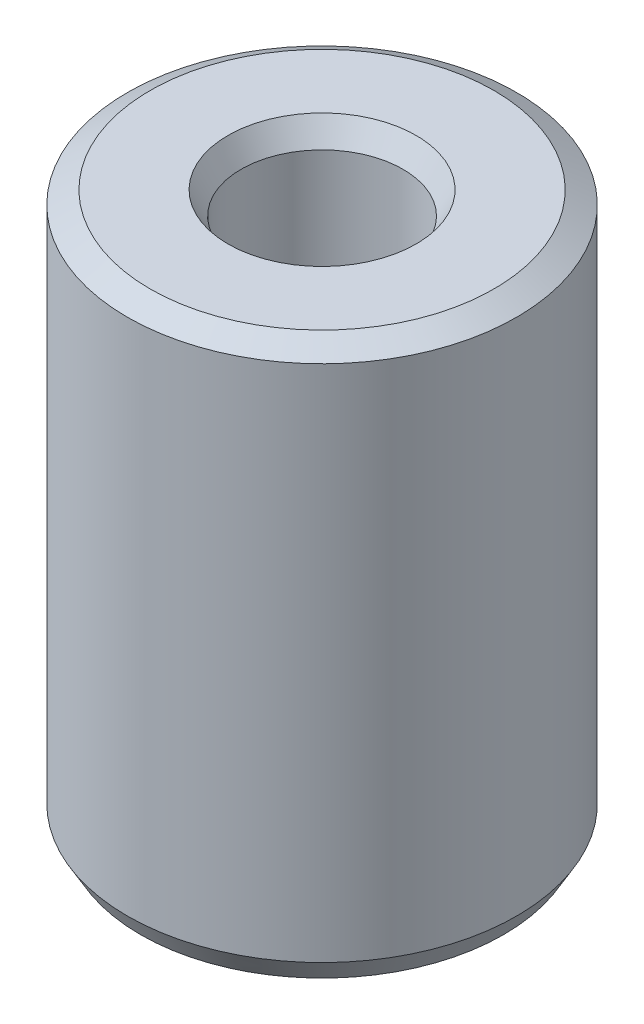
SolidWorks part; units mm, degrees
ref_plane "Front Plane" through (0, 0, 0) normal (0, 0, 1) x (1, 0, 0)
ref_plane "Top Plane" through (0, 0, 0) normal (0, 1, 0) x (1, 0, 0)
ref_plane "Right Plane" through (0, 0, 0) normal (1, 0, 0) x (0, 0, -1)
sketch "Sketch1" plane through (0, 0, 0) normal (0, 1, 0) x (1, 0, 0)
  circle A0 centre (0, 0) radius 47.5
  dimension "SLEEVE_OD" = 95
extrude "Boss-Extrude1" add sketch "Sketch1" along normal blind 135.2945
sketch "Sketch2" plane through (0, 0, 0) normal (0, 1, 0) x (1, 0, 0)
  circle A0 centre (0, 0) radius 19.7553
  dimension "BORE_D" = 39.5106
extrude "Cut-Extrude1" cut sketch "Sketch2" along normal through all
chamfer "Chamfer1" distance 3.201 angle 60 4 edges at (0, 135.2945, 19.7553) (0, 0, 19.7553) (0, 0, 47.5) (0, 135.2945, 47.5) first distance on face at (0, 135.2945, 19.7553) first distance on face at (0, 0, 19.7553) first distance on face at (0, 135.2945, 47.5)
